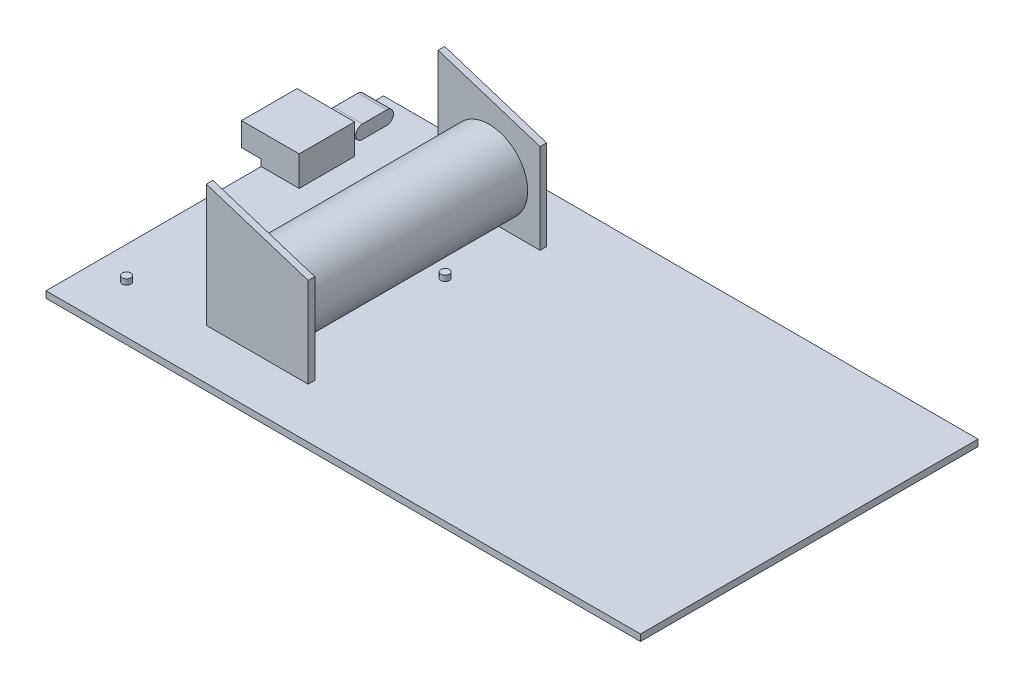
SolidWorks part; units mm, degrees
ref_plane "Front Plane" through (0, 0, 0) normal (0, 0, 1) x (1, 0, 0)
ref_plane "Top Plane" through (0, 0, 0) normal (0, 1, 0) x (1, 0, 0)
ref_plane "Right Plane" through (0, 0, 0) normal (1, 0, 0) x (0, 0, -1)
sketch "Sketch1" plane through (0, 0, 0) normal (0, 1, 0) x (1, 0, 0)
  line L1 (-70.45, -40) -> (70.45, -40)
  line L2 (-70.45, -40) -> (-70.45, 40)
  line L3 (-70.45, 40) -> (70.45, 40)
  line L4 (70.45, -40) -> (70.45, 40)
  line L5 (-70.45, -40) -> (70.45, 40) construction
  line L6 (-70.45, 40) -> (70.45, -40) construction
  point P0 (0, 0)
  dimension "D1" = 140.9
  dimension "D2" = 80
extrude "PCB" add sketch "Sketch1" along normal blind 1.55
sketch "Sketch2" plane through (-70.45, 0, 0) normal (-1, 0, 0) x (0, 0, 1)
  line L0 (-31.43, 1.55) -> (-31.43, 3.15)
  line L1 (-40, 1.55) -> (40, 1.55) construction
  line L2 (-40, 1.55) -> (-40, 0) construction
  dimension "D1" = 1.6
  dimension "D2" = 8.57
sketch "Sketch3" plane through (-70.45, 0, 0) normal (-1, 0, 0) x (0, 0, 1)
  line L0 (-34.3, 3.15) -> (-28.56, 3.15) construction
  line L1 (-34.3, 4.75) -> (-28.56, 4.75)
  line L2 (-34.3, 1.55) -> (-28.56, 1.55)
  arc A0 (-34.3, 4.75) -> (-34.3, 1.55) centre (-34.3, 3.15) ccw
  arc A1 (-28.56, 1.55) -> (-28.56, 4.75) centre (-28.56, 3.15) ccw
  point P2 (-31.43, 3.15)
  dimension "D1" = 5.74
extrude "bodyC" add sketch "Sketch3" against normal blind 6.45 and the other way blind 0.4
sketch "Sketch4" plane through (0, 1.55, 0) normal (0, 1, 0) x (1, 0, 0)
  line L0 (70.45, 40) -> (-70.45, 40) construction
  line L1 (-61.45, 11) -> (-75.1, 11)
  line L2 (-61.45, 11) -> (-61.45, 24.15)
  line L3 (-61.45, 24.15) -> (-75.1, 24.15)
  line L4 (-75.1, 11) -> (-75.1, 24.15)
  line L6 (-70.45, 28.56) -> (-70.45, -40) construction
  dimension "D1" = 13.65
  dimension "D2" = 13.15
  dimension "D3" = 15.85
  dimension "D4" = 4.65
extrude "Boss-Extrude4" add sketch "Sketch4" along normal blind 7.1 and the other way blind 1.55
sketch "Sketch5" plane through (0, 0, -11) normal (0, 0, 1) x (1, 0, 0)
  line L0 (-75.1, 0) -> (-75.1, 8.65) construction
  line L1 (-70.45, 0) -> (-75.1, 0)
  line L2 (-70.45, 0) -> (-70.45, 3.1)
  line L3 (-70.45, 3.1) -> (-75.1, 3.1)
  line L4 (-75.1, 0) -> (-75.1, 3.1)
  dimension "D1" = 3.1
extrude "Cut-Extrude3" cut sketch "Sketch5" against normal blind 14.1
sketch "Sketch11" plane through (0, 1.55, 0) normal (0, 1, 0) x (1, 0, 0)
  line L1 (-44.35, 26.85) -> (-20.2, 26.85)
  line L2 (-44.35, 26.85) -> (-44.35, 28.4)
  line L3 (-44.35, 28.4) -> (-20.2, 28.4)
  line L4 (-20.2, 26.85) -> (-20.2, 28.4)
  line L6 (70.45, 40) -> (-70.45, 40) construction
  line L7 (-70.45, 40) -> (-70.45, 34.3) construction
  dimension "D1" = 11.6
  dimension "D2" = 26.1
  dimension "D3" = 1.55
  dimension "D4" = 24.15
extrude "Boss-Extrude8" add sketch "Sketch11" along normal blind 29
sketch "Sketch7" plane through (0, 1.55, 0) normal (0, 1, 0) x (1, 0, 0)
  line L0 (-70.45, 11) -> (-70.45, -40) construction
  line L1 (-44.35, -28.1) -> (-20.2, -28.1)
  line L2 (-44.35, -28.1) -> (-44.35, -26.55)
  line L3 (-44.35, -26.55) -> (-20.2, -26.55)
  line L4 (-20.2, -28.1) -> (-20.2, -26.55)
  line L5 (-70.45, -40) -> (70.45, -40) construction
  dimension "D1" = 26.1
  dimension "D2" = 11.9
  dimension "D3" = 1.55
  dimension "D4" = 24.15
extrude "Boss-Extrude5" add sketch "Sketch7" along normal blind 29
sketch "Sketch8" plane through (0, 0, 28.1) normal (0, 0, 1) x (1, 0, 0)
  line L0 (-44.35, 30.55) -> (-20.2, 22.85)
  line L1 (-20.2, 30.55) -> (-20.2, 1.55) construction
  line L5 (-20.2, 30.55) -> (-44.35, 30.55)
  line L6 (-20.2, 22.85) -> (-20.2, 30.55)
extrude "Cut-Extrude4" cut sketch "Sketch8" against normal blind 89
sketch "Sketch12" plane through (0, 0, -26.85) normal (0, 0, 1) x (1, 0, 0)
  line L0 (-32.275, 1.55) -> (-32.275, 12.25)
  line L1 (-44.35, 1.55) -> (-20.2, 1.55) construction
  circle A0 centre (-32.275, 12.25) radius 9.15
  dimension "D1" = 10.7
extrude "Battery" add sketch "Sketch12" along normal blind 54 contours A0 region at (-25.988, 5.963, -26.85)
sketch "Sketch13" plane through (0, 1.55, 0) normal (0, 1, 0) x (1, 0, 0)
  line L0 (-70.45, -28.6) -> (-62.75, -28.6)
  line L1 (-70.45, 11) -> (-70.45, -40) construction
  line L2 (-70.45, -40) -> (70.45, -40) construction
  circle A0 centre (-62.75, -28.6) radius 1
  dimension "D1" = 7.7
  dimension "D2" = 11.4
extrude "Button" add sketch "Sketch13" along normal blind 1.3 contours A0
sketch "Sketch14" plane through (0, 1.55, 0) normal (0, 1, 0) x (1, 0, 0)
  line L0 (-33.45, 9.9) -> (-25.75, 9.9)
  line L3 (70.45, 40) -> (-70.45, 40) construction
  line L4 (70.45, -40) -> (70.45, 40) construction
  circle A0 centre (-25.75, 9.9) radius 1
  dimension "D3" = 96.2
  dimension "D2" = 30.1
  dimension "D1" = 7.7
extrude "Reset" add sketch "Sketch14" along normal blind 1.3 contours A0
